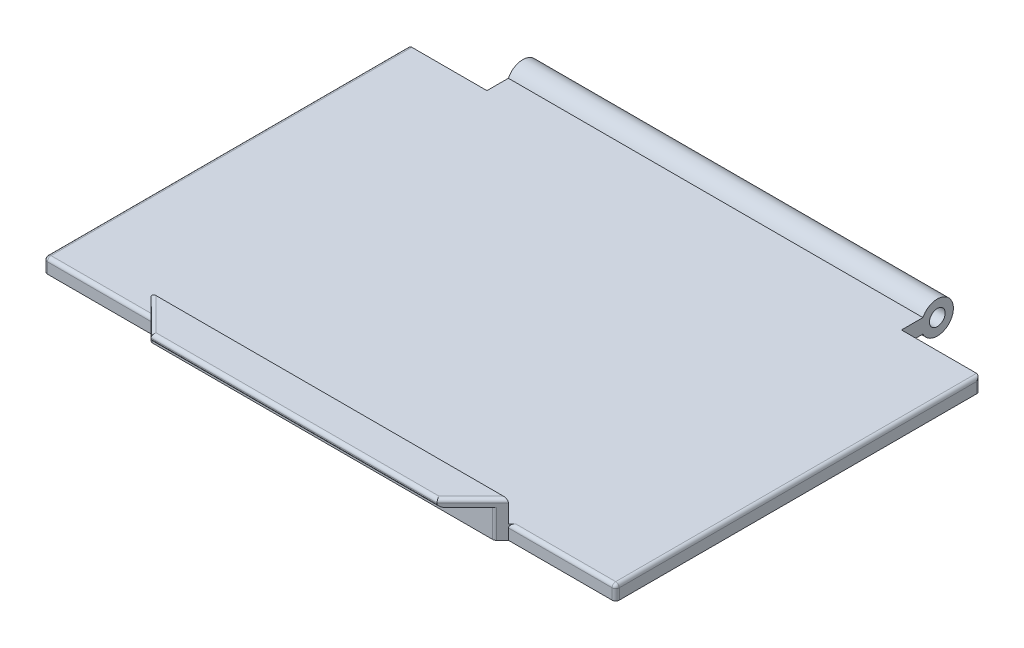
SolidWorks part; units mm, degrees
ref_plane "Front Plane" through (0, 0, 0) normal (0, 0, 1) x (1, 0, 0)
ref_plane "Top Plane" through (0, 0, 0) normal (0, 1, 0) x (1, 0, 0)
ref_plane "Right Plane" through (0, 0, 0) normal (1, 0, 0) x (0, 0, -1)
sketch "Sketch2" plane through (0, 0, 0) normal (1, 0, 0) x (0, 0, -1)
  line L0 (0, 0) -> (-57, 0) construction
  line L1 (-2.0156, 1) -> (-56, 1)
  line L2 (-2.0156, -1) -> (-57, -1)
  line L4 (-57, 1) -> (-57, -1)
  line L5 (-57, 1) -> (-57, 3)
  line L6 (-57, 3) -> (-61, 3)
  line L7 (-61, 3) -> (-61, 4)
  line L8 (-61, 4) -> (-56, 4)
  line L9 (-56, 4) -> (-56, 1)
  line L11 (0, 1) -> (-57, 1) construction
  line L12 (0, -1) -> (-57, -1) construction
  arc A0 (-2.0156, -1) -> (-2.25, 0) centre (0, 0) ccw
  circle A1 centre (0, 0) radius 1.1
  dimension "D1" = 4.5
  dimension "D9" = 2.2
  dimension "D2" = 57
  dimension "D5" = 5
  dimension "D6" = 3
  dimension "D7" = 1
  dimension "D8" = 1
  dimension "D3" = 1
  dimension "D4" = 1
extrude "Boss-Extrude1" add sketch "Sketch2" against normal blind 80 contours L2 A0 L1 L9 L8 L7 L6 L5 L4 A1 region at (0, 0.167, 28.3464)
ref_plane "Plane1" through (-40, 0, 0) normal (1, 0, 0) x (0, 0, -1)
sketch "Sketch5" plane through (-40, 0, 0) normal (1, 0, 0) x (0, 0, -1)
  line L0 (-2.0156, 1) -> (-5.0156, 1)
  line L1 (-2.0156, 1) -> (-56, 1) construction
  line L2 (-5.0156, 1) -> (-5.0156, -1)
  line L3 (-2.0156, -1) -> (-57, -1) construction
  line L4 (-5.0156, -1) -> (-2.0156, -1)
  arc A0 (-2.0156, -1) -> (-2.0156, 1) centre (0, 0) ccw
  dimension "D1" = 3
extrude "Cut-Extrude1" cut sketch "Sketch5" against normal blind 11 from offset 40
mirror "Mirror1" about plane through (-40, 0, 0) normal (1, 0, 0) of "Cut-Extrude1"
sketch "Sketch6" plane through (0, 4, 0) normal (0, 1, 0) x (1, 0, 0)
  line L2 (-80, -56) -> (0, -56) construction
  line L3 (-65, -56) -> (-60, -61)
  line L4 (-80, -61) -> (0, -61) construction
  line L7 (-40, -1.1) -> (-40, 1.1) construction
  line L8 (-15, -56) -> (-20, -61)
  line L9 (-65, -56) -> (-80, -56)
  line L10 (-80, -56) -> (-80, -61)
  line L11 (-80, -61) -> (-60, -61)
  line L12 (-15, -56) -> (0, -56)
  line L13 (0, -56) -> (0, -61)
  line L14 (0, -61) -> (-20, -61)
  dimension "D1" = 20
  dimension "D2" = 50
extrude "Cut-Extrude2" cut sketch "Sketch6" against normal through all
fillet "Fillet1" radius 0.5 14 edges at (-17.5, 4, 58.5) (-62.5, 4, 58.5) (-40, 4, 61) (0, 0, 5.0156) (0, 0, 56) (-80, 0, 5.0156) (-80, 0, 56) (-40, 3, 61) (-16, 1, 57) (-64, 1, 57) (-72.5, 1, 56) (-7.5, 1, 56) (0, 1, 30.5078) (-80, 1, 30.5078)
equation "\"H\"= 3"
equation "\"D1@Sketch5\"=\"H\""
equation "\"L\"= 57"
equation "\"D2@Sketch2\"=\"L\""
